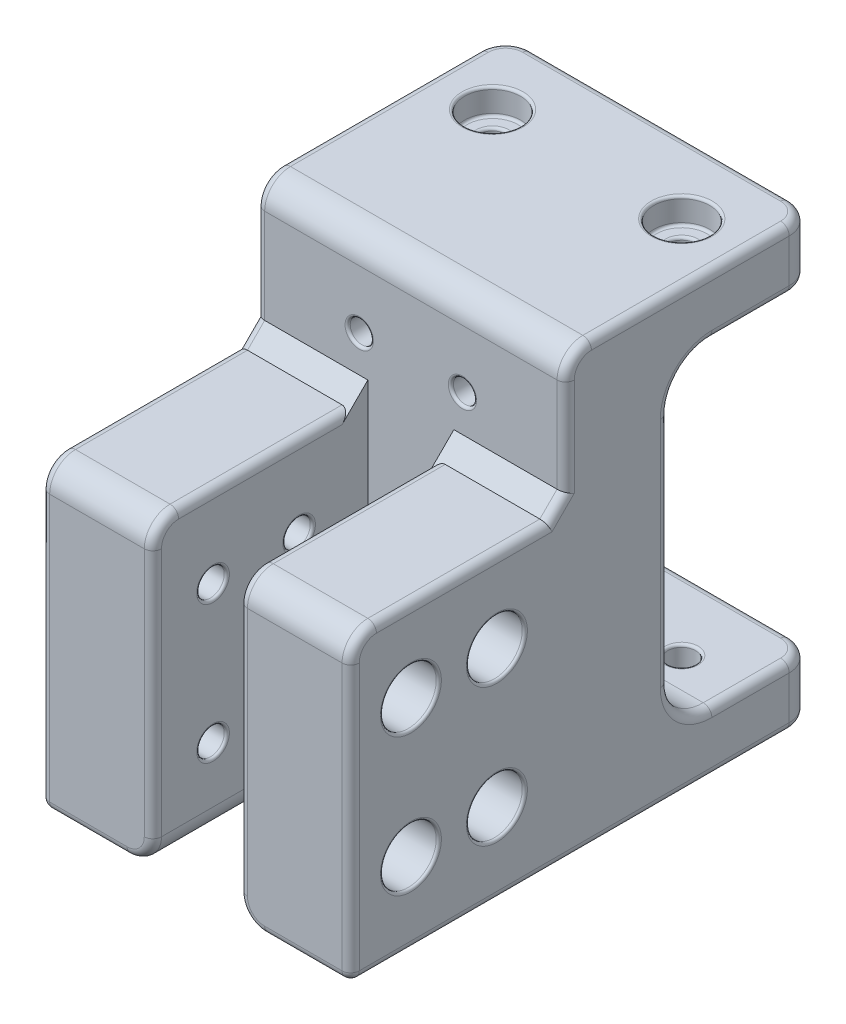
SolidWorks part; units mm, degrees
ref_plane "정면" through (0, 0, 0) normal (0, 0, 1) x (1, 0, 0)
ref_plane "윗면" through (0, 0, 0) normal (0, 1, 0) x (1, 0, 0)
ref_plane "우측면" through (0, 0, 0) normal (1, 0, 0) x (0, 0, -1)
sketch "스케치1" plane through (0, 0, 0) normal (1, 0, 0) x (0, 0, -1)
  line L0 (8.5, 18.5) -> (8.5, 25.5)
  line L1 (-8.5, 18.5) -> (8.5, 18.5)
  line L2 (-8.5, 18.5) -> (-8.5, -18.5)
  line L3 (-8.5, -18.5) -> (8.5, -18.5)
  line L5 (-8.5, 18.5) -> (8.5, -18.5) construction
  line L6 (-8.5, -18.5) -> (8.5, 18.5) construction
  line L7 (8.5, 25.5) -> (-20.5, 25.5)
  line L8 (-20.5, 25.5) -> (-20.5, -25.5)
  line L9 (-20.5, -25.5) -> (8.5, -25.5)
  line L10 (8.5, -25.5) -> (8.5, -18.5)
  point P0 (0, 0)
  dimension "D1" = 37
  dimension "D2" = 7
  dimension "D3" = 7
  dimension "D4" = 12
  dimension "D5" = 17
  dimension "D6" = 8.5
extrude "보스-돌출1" add sketch "스케치1" along normal mid plane 36
sketch "스케치2" plane through (0, 0, 0) normal (1, 0, 0) x (0, 0, -1)
  line L1 (-45.5, 9.5) -> (-20.5, 9.5)
  line L2 (-45.5, 9.5) -> (-45.5, -25.5)
  line L3 (-45.5, -25.5) -> (-20.5, -25.5)
  line L4 (-20.5, 9.5) -> (-20.5, -25.5)
  dimension "D1" = 35
  dimension "D2" = 25
extrude "보스-돌출2" add sketch "스케치2" along normal mid plane 36
sketch "스케치3" plane through (0, 0, 0) normal (1, 0, 0) x (0, 0, -1)
  line L0 (-45.5, -25.5) -> (8.5, -25.5) construction
  line L1 (-45.5, 9.5) -> (-20.5, 9.5)
  line L2 (-45.5, 9.5) -> (-45.5, -25.5)
  line L3 (-45.5, -25.5) -> (-20.5, -25.5)
  line L4 (-20.5, 9.5) -> (-20.5, -25.5)
  line L5 (-20.5, 25.5) -> (-20.5, 9.5) construction
extrude "컷-돌출1" cut sketch "스케치3" against normal mid plane 10
hole_wizard "M3 소켓 머리 캡 나사용 카운터보어1" positions "스케치4" profile "스케치5" counterbore size "M3" standard "KS" end condition through all
sketch "스케치4" plane through (18, 0, 0) normal (1, 0, 0) x (0, 0, -1)
  line L0 (-45.5, 9.5) -> (-45.5, -25.5) construction
  line L1 (-20.5, 9.5) -> (-45.5, 9.5) construction
  line L2 (-45.5, -25.5) -> (8.5, -25.5) construction
  point P0 (-38.5, 0)
  point P2 (-28.5, 0)
  point P4 (-38.5, -16)
  point P6 (-28.5, -16)
  point P9 (0, 0)
  point P10 (0, 0)
  point P11 (0, 0)
  point P12 (0, 0)
  point P13 (0, 0)
  point P14 (-24.638, -14.318)
  dimension "D1" = 7
  dimension "D2" = 9.5
  dimension "D3" = 9.5
  dimension "D4" = 10
sketch "스케치5" plane through (18, 0, 38.5) normal (0, 1, 0) x (0, 0, -1)
  line L0 (0, 0) -> (0, 36)
  line L1 (0, 36) -> (1.6, 36)
  line L3 (1.6, 36) -> (1.6, 6)
  line L4 (1.6, 6) -> (3.25, 6)
  line L5 (3.25, 6) -> (3.25, 0)
  line L7 (3.25, 0) -> (0, 0)
  line L11 (0, -6.35) -> (0, 107.95) construction
  dimension "관통 구멍 지름" = 3.2
  dimension "관통 구멍 깊이" = 36
  dimension "카운터보어 지름" = 6.5
  dimension "카운터보어 깊이" = 6
sketch "스케치6" plane through (-18, 0, 0) normal (-1, 0, 0) x (0, 0, 1)
  line L1 (25.775, 2.725) -> (31.225, 2.725)
  line L2 (25.775, 2.725) -> (25.775, -2.725)
  line L3 (25.775, -2.725) -> (31.225, -2.725)
  line L4 (31.225, 2.725) -> (31.225, -2.725)
  line L5 (25.775, 2.725) -> (31.225, -2.725) construction
  line L6 (25.775, -2.725) -> (31.225, 2.725) construction
  line L7 (35.775, 2.725) -> (41.225, 2.725)
  line L8 (35.775, 2.725) -> (35.775, -2.725)
  line L9 (35.775, -2.725) -> (41.225, -2.725)
  line L10 (41.225, 2.725) -> (41.225, -2.725)
  line L11 (35.775, 2.725) -> (41.225, -2.725) construction
  line L12 (35.775, -2.725) -> (41.225, 2.725) construction
  line L13 (25.775, -13.275) -> (31.225, -13.275)
  line L14 (25.775, -13.275) -> (25.775, -18.725)
  line L15 (25.775, -18.725) -> (31.225, -18.725)
  line L16 (31.225, -13.275) -> (31.225, -18.725)
  line L17 (25.775, -13.275) -> (31.225, -18.725) construction
  line L18 (25.775, -18.725) -> (31.225, -13.275) construction
  line L19 (35.775, -13.275) -> (41.225, -13.275)
  line L20 (35.775, -13.275) -> (35.775, -18.725)
  line L21 (35.775, -18.725) -> (41.225, -18.725)
  line L22 (41.225, -13.275) -> (41.225, -18.725)
  line L23 (35.775, -13.275) -> (41.225, -18.725) construction
  line L24 (35.775, -18.725) -> (41.225, -13.275) construction
  point P0 (28.5, 0)
  point P5 (38.5, 0)
  point P11 (28.5, -16)
  point P17 (38.5, -16)
  dimension "D1" = 5.45
  dimension "D2" = 5.45
  dimension "D3" = 5.45
  dimension "D4" = 5.45
  dimension "D5" = 5.45
  dimension "D6" = 5.45
  dimension "D7" = 5.45
  dimension "D8" = 5.45
extrude "컷-돌출2" cut sketch "스케치6" against normal blind 2.45
hole_wizard "M3 소켓 머리 캡 나사용 카운터보어2" positions "스케치7" profile "스케치8" counterbore size "M3" standard "KS" end condition up to next
sketch "스케치7" plane through (0, 25.5, 0) normal (0, 1, 0) x (1, 0, 0)
  point P0 (11, 0)
  point P3 (-11, 0)
sketch "스케치8" plane through (11, 25.5, 0) normal (1, 0, 0) x (0, 0, 1)
  line L0 (0, 0) -> (0, 7)
  line L1 (0, 7) -> (1.6, 7)
  line L3 (1.6, 7) -> (1.6, 3)
  line L4 (1.6, 3) -> (3.25, 3)
  line L5 (3.25, 3) -> (3.25, 0)
  line L7 (3.25, 0) -> (0, 0)
  line L11 (0, -6.35) -> (0, 107.95) construction
  dimension "관통 구멍 지름" = 3.2
  dimension "관통 구멍 깊이" = 7
  dimension "카운터보어 지름" = 6.5
  dimension "카운터보어 깊이" = 3
hole_wizard "M3 소켓 머리 캡 나사용 카운터보어3" positions "스케치9" profile "스케치10" counterbore size "M3" standard "KS" end condition up to next
sketch "스케치9" plane through (0, -25.5, 0) normal (0, -1, 0) x (-1, 0, 0)
  point P0 (-11, 0)
  point P3 (11, 0)
sketch "스케치10" plane through (11, -25.5, 0) normal (1, 0, 0) x (0, 0, -1)
  line L0 (0, 0) -> (0, 7)
  line L1 (0, 7) -> (1.6, 7)
  line L3 (1.6, 7) -> (1.6, 3)
  line L4 (1.6, 3) -> (3.25, 3)
  line L5 (3.25, 3) -> (3.25, 0)
  line L7 (3.25, 0) -> (0, 0)
  line L11 (0, -6.35) -> (0, 107.95) construction
  dimension "관통 구멍 지름" = 3.2
  dimension "관통 구멍 깊이" = 7
  dimension "카운터보어 지름" = 6.5
  dimension "카운터보어 깊이" = 3
fillet "필렛2" radius 3 2 edges at (-5, -25.5, 33) (5, -25.5, 33)
hole_wizard "M2.5 소켓 머리 캡 나사용 카운터보어1" positions "스케치11" profile "스케치12" counterbore size "M2.5" standard "KS" end condition through all
sketch "스케치11" plane through (0, 0, 8.5) normal (0, 0, -1) x (-1, 0, 0)
  point P0 (-6, 15.75)
  point P3 (6, 15.75)
sketch "스케치12" plane through (6, 15.75, 8.5) normal (1, 0, 0) x (0, 1, 0)
  line L0 (0, 0) -> (0, 37)
  line L1 (0, 37) -> (1.35, 37)
  line L3 (1.35, 37) -> (1.35, 2.5)
  line L4 (1.35, 2.5) -> (2.75, 2.5)
  line L5 (2.75, 2.5) -> (2.75, 0)
  line L7 (2.75, 0) -> (0, 0)
  line L11 (0, -6.35) -> (0, 107.95) construction
  dimension "관통 구멍 지름" = 2.7
  dimension "관통 구멍 깊이" = 37
  dimension "카운터보어 지름" = 5.5
  dimension "카운터보어 깊이" = 2.5
fillet "필렛3" radius 5 4 edges at (-12, 18.5, 8.5) (12, 18.5, 8.5) (0, 18.5, 8.5) (0, -18.5, 8.5)
fillet "필렛4" radius 0.3 12 edges at (6, 13, 8.5) (6, 17.1, 20.5) (-6, 13, 8.5) (-6, 18.5, 11) (-6, 17.1, 20.5) (-8.7479, 15.6422, 8.0178) (-3.2521, 15.6422, 8.0178) (8.7479, 15.6422, 8.0178) (-6, 17.1, 11) (6, 17.1, 11) (6, 18.5, 11) (3.2521, 15.6422, 8.0178)
fillet "필렛5" radius 3 2 edges at (11.5, 9.5, 45.5) (-11.5, 9.5, 45.5)
chamfer "모따기1" distance 2 angle 45 2 edges at (-11.5, 9.5, 20.5) (11.5, 9.5, 20.5)
fillet "필렛6" radius 3 1 edges at (0, 25.5, 20.5)
fillet "필렛7" radius 3 4 edges at (18, -22, -8.5) (-18, -22, -8.5) (-18, 22, -8.5) (18, 22, -8.5)
fillet "필렛8" radius 1 10 edges at (-5, 9.5, 32.5) (-5, 8.6213, 44.6213) (-13, -25.5, 45.5) (-5.8787, -24.6213, 45.5) (5, 9.5, 32.5) (5, 8.6213, 44.6213) (13, -25.5, 45.5) (5.8787, -24.6213, 45.5) (-5, -8, 45.5) (5, -8, 45.5)
fillet "필렛9" radius 1 13 edges at (-18, 9.5, 32.5) (-18, 8.6213, 44.6213) (-18, -9, 45.5) (-18, -25.2071, 45.2071) (18, 9.5, 32.5) (18, 8.6213, 44.6213) (18, -9, 45.5) (18, -25.2071, 45.2071) (18, -25.5, 19.5) (17.1213, -25.5, -7.6213) (0, -25.5, -8.5) (-17.1213, -25.5, -7.6213) (-18, -25.5, 19.5)
fillet "필렛10" radius 0.3 72 edges at (-16.775, -18.725, 41.225) (-16.775, -18.725, 35.775) (-16.775, -13.275, 35.775) (-16.775, -13.275, 41.225) (-15.55, -18.725, 38.5) (-15.55, -16, 35.775) (-15.55, -13.275, 38.5) (-15.55, -16, 41.225) (-16.775, -18.725, 31.225) (-16.775, -18.725, 25.775) (-16.775, -13.275, 25.775) (-16.775, -13.275, 31.225) (-15.55, -18.725, 28.5) (-15.55, -16, 25.775) (-15.55, -13.275, 28.5) (-15.55, -16, 31.225) (-16.775, -2.725, 41.225) (-16.775, -2.725, 35.775) (-16.775, 2.725, 35.775) (-16.775, 2.725, 41.225) (-15.55, -2.725, 38.5) (-15.55, 0, 35.775) (-15.55, 2.725, 38.5) (-15.55, 0, 41.225) (-15.55, 0, 31.225) (-15.55, 0, 25.775) (-15.55, -2.725, 28.5) (-16.775, 2.725, 31.225) (-16.775, 2.725, 25.775) (-16.775, -2.725, 25.775) (-16.775, -2.725, 31.225) (-15.55, 2.725, 28.5) (-18, 0, 25.775) (-18, -2.725, 28.5) (-18, 0, 31.225) (-18, -13.275, 38.5) (-18, -16, 35.775) (-18, -18.725, 38.5) (-18, -16, 41.225) (-18, -13.275, 28.5) (-18, -16, 25.775) (-18, -18.725, 28.5) (-18, -16, 31.225) (-18, 2.725, 38.5) (-18, 0, 35.775) (-18, -2.725, 38.5) (-18, 0, 41.225) (-18, 2.725, 28.5) (-15.55, 0, 40.1) (-15.55, 0, 30.1) (-15.55, -16, 40.1) (-15.55, -16, 30.1) (5, 0, 36.9) (-5, 0, 36.9) (18, 0, 25.25) (12, 0, 25.25) (12, 0, 26.9) (5, 0, 26.9) (-5, 0, 26.9) (18, -16, 35.25) (12, -16, 35.25) (12, -16, 36.9) (-5, -16, 36.9) (5, -16, 36.9) (18, -16, 25.25) (12, -16, 25.25) (12, -16, 26.9) (-5, -16, 26.9) (5, -16, 26.9) (12, 0, 36.9) (12, 0, 35.25) (18, 0, 35.25)
fillet "필렛11" radius 1 11 edges at (18, 17, 20.5) (18, 24.6213, 19.6213) (18, 25.5, 6) (17.1213, 25.5, -7.6213) (0, 25.5, -8.5) (-17.1213, 25.5, -7.6213) (-18, 25.5, 6) (-18, 24.6213, 19.6213) (-18, 17, 20.5) (18, 10, 22) (-18, 10, 22)
fillet "필렛12" radius 0.3 16 edges at (11, -22.5, -1.6) (-11, -22.5, -3.25) (-11, -22.5, -1.6) (11, -22.5, -3.25) (11, -25.5, -3.25) (11, -18.5, -1.6) (-11, -18.5, -1.6) (-11, -25.5, -3.25) (11, 25.5, 3.25) (11, 22.5, 3.25) (11, 22.5, 1.6) (11, 18.5, 1.6) (-11, 22.5, 1.6) (-11, 18.5, 1.6) (-11, 22.5, 3.25) (-11, 25.5, 3.25)
fillet "필렛13" radius 1 16 edges at (-18, -17.0355, 7.0355) (-18, -18.5, -1) (-17.1213, -18.5, -7.6213) (0, -18.5, -8.5) (17.1213, -18.5, -7.6213) (18, -18.5, -1) (18, -17.0355, 7.0355) (18, 0, 8.5) (18, 17.0355, 7.0355) (18, 18.5, -1) (17.1213, 18.5, -7.6213) (0, 18.5, -8.5) (-17.1213, 18.5, -7.6213) (-18, 18.5, -1) (-18, 17.0355, 7.0355) (-18, 0, 8.5)
